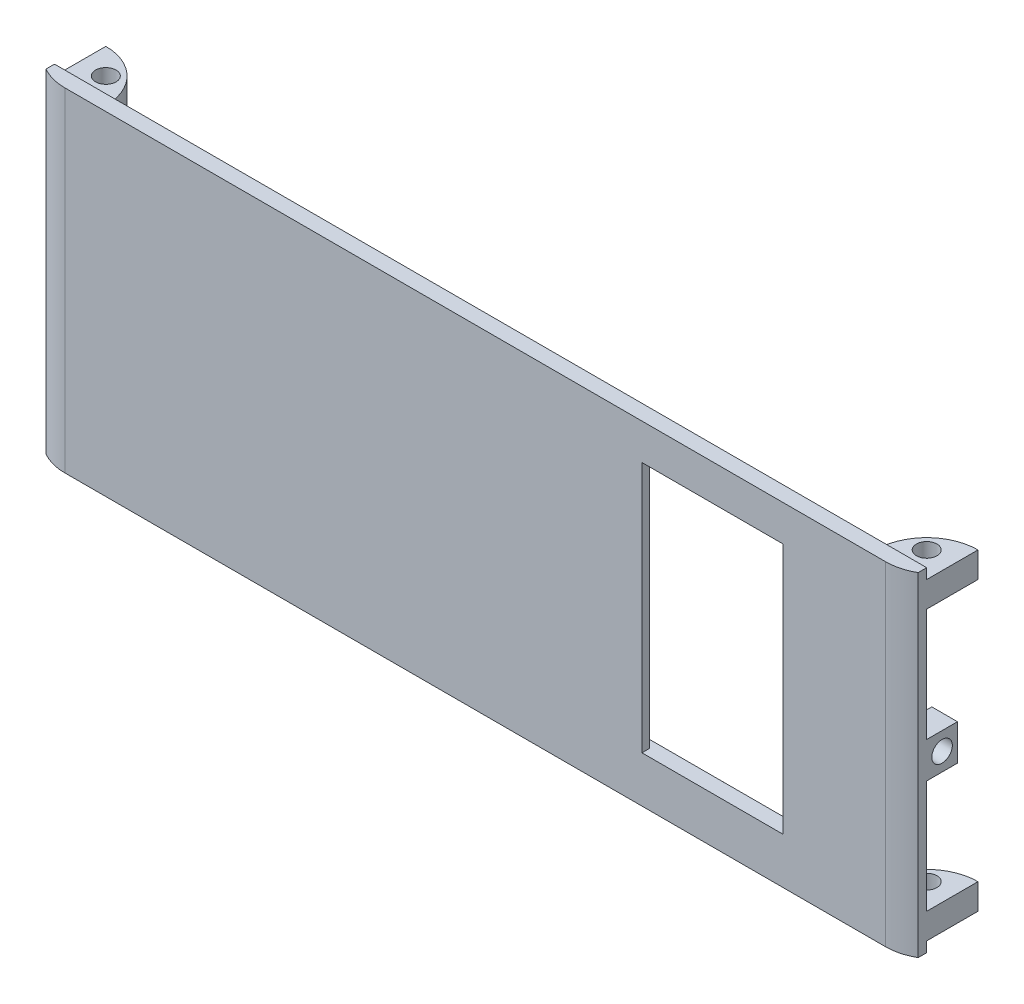
SolidWorks part; units mm, degrees
material "Allzweck-PBT"
ref_plane "Ebene vorne" through (0, 0, 0) normal (0, 0, 1) x (1, 0, 0)
ref_plane "Ebene oben" through (0, 0, 0) normal (0, 1, 0) x (1, 0, 0)
ref_plane "Ebene rechts" through (0, 0, 0) normal (1, 0, 0) x (0, 0, -1)
sketch "Skizze1" plane through (0, 0, 0) normal (0, 0, 1) x (1, 0, 0)
  line L1 (-90, 32.5) -> (90, 32.5)
  line L2 (-90, 32.5) -> (-90, -32.5)
  line L3 (-90, -32.5) -> (90, -32.5)
  line L4 (90, 32.5) -> (90, -32.5)
  line L5 (-90, 32.5) -> (90, -32.5) construction
  line L6 (-90, -32.5) -> (90, 32.5) construction
  point P0 (0, 0)
  dimension "D1" = 180
  dimension "3" = 65
extrude "Aufsatz-Linear austragen1" add sketch "Skizze1" along normal blind 3
sketch "Skizze3" plane through (0, 0, 0) normal (0, 0, -1) x (-1, 0, 0)
  line L0 (-90, -32.5) -> (-90, 32.5) construction
  line L9 (-85, 3.5) -> (-80, 3.5)
  line L10 (-85, 3.5) -> (-85, -3.5)
  line L11 (-85, -3.5) -> (-80, -3.5)
  line L12 (-80, 3.5) -> (-80, -3.5)
  line L13 (-85, 3.5) -> (-80, -3.5) construction
  line L14 (-85, -3.5) -> (-80, 3.5) construction
  line L15 (80, 3.5) -> (85, 3.5)
  line L16 (80, 3.5) -> (80, -3.5)
  line L17 (80, -3.5) -> (85, -3.5)
  line L18 (85, 3.5) -> (85, -3.5)
  line L19 (80, 3.5) -> (85, -3.5) construction
  line L20 (80, -3.5) -> (85, 3.5) construction
  line L21 (90, 32.5) -> (90, -32.5) construction
  line L23 (-90, 32.5) -> (90, 32.5) construction
  point P0 (-82.5, 0)
  point P5 (82.5, 0)
  dimension "D1" = 5
  dimension "D2" = 5
  dimension "7" = 7
  dimension "D3" = 5
  dimension "D4" = 7
  dimension "D5" = 5
  dimension "D6" = 32.5
  dimension "D7" = 32.5
extrude "Aufsatz-Linear austragen2" add sketch "Skizze3" along normal blind 6
hole_wizard "Ø4.0 (4) Durchmesser Bohrung1" positions "Skizze4" profile "Skizze5" hole size "Ø4.0" standard "DIN" end condition through all
sketch "Skizze4" plane through (-85, 0, 0) normal (-1, 0, 0) x (0, 0, 1)
  line L0 (0, -3.5) -> (0, 3.5) construction
  line L1 (-6, 3.5) -> (0, 3.5) construction
  point P0 (-3, 0)
  dimension "D1" = 3
  dimension "D2" = 3.5
sketch "Skizze5" plane through (-85, 0, -3) normal (0, 1, 0) x (0, 0, 1)
  line L0 (0, 0) -> (0, 175)
  line L1 (0, 175) -> (2, 175)
  line L2 (2, 175) -> (2, 0)
  line L5 (2, 0) -> (0, 0)
  line L11 (0, -6.35) -> (0, 107.95) construction
  dimension "Bohrerdurchmesser" = 4
  dimension "Bohrungstiefe" = 175
sketch "Skizze6" plane through (0, 32.5, 0) normal (0, 1, 0) x (1, 0, 0)
  line L0 (-80, -3) -> (-90, -3)
  line L9 (-90, -3) -> (-90, 0)
  line L10 (-90, 0) -> (-85, 0)
  line L11 (-85, 0) -> (-85, -1.6603)
  line L12 (80, -3) -> (90, -3)
  line L13 (90, -3) -> (90, 0)
  line L14 (90, 0) -> (85, 0)
  line L15 (85, 0) -> (85, -1.6603)
  arc A0 (80, -3) -> (85, -1.6603) centre (80, 7) ccw
  arc A1 (-80, -3) -> (-85, -1.6603) centre (-80, 7) cw
  point P12 (90, -3)
  point P15 (-90, -3)
  dimension "D1" = 10
  dimension "D3" = 10
  dimension "D2" = 1.3397
  dimension "D4" = 1.3397
  dimension "D5" = 10
extrude "Schnitt-Linear austragen1" cut sketch "Skizze6" against normal through all
sketch "Skizze7" plane through (0, 0, 3) normal (0, 0, 1) x (1, 0, 0)
  line L0 (80, -32.5) -> (80, 32.5) construction
  line L1 (32.5, 25.5) -> (60, 25.5)
  line L2 (32.5, 25.5) -> (32.5, -23.5)
  line L3 (32.5, -23.5) -> (60, -23.5)
  line L4 (60, 25.5) -> (60, -23.5)
  line L5 (-80, -32.5) -> (80, -32.5) construction
  dimension "D1" = 49
  dimension "D2" = 27.5
  dimension "D3" = 20
  dimension "D4" = 9
extrude "Schnitt-Linear austragen2" cut sketch "Skizze7" against normal through all
sketch "Skizze8" plane through (0, 0, 0) normal (0, 0, -1) x (-1, 0, 0)
  line L0 (-85, 32.5) -> (85, 32.5) construction
  line L1 (-85, 30.5) -> (-75, 30.5)
  line L2 (-85, 30.5) -> (-85, 25.5)
  line L3 (-85, 25.5) -> (-75, 25.5)
  line L4 (-75, 30.5) -> (-75, 25.5)
  line L5 (-85, 3.5) -> (-85, 32.5) construction
  dimension "D1" = 2
  dimension "D2" = 10
  dimension "D3" = 5
extrude "Aufsatz-Linear austragen3" add sketch "Skizze8" along normal blind 10
mirror "Spiegeln1" about plane through (0, 0, 0) normal (1, 0, 0) of "Aufsatz-Linear austragen3" second plane through (0, 0, 0) second plane normal (0, 1, 0)
fillet "Verrundung1" radius 10 20 edges at (75, 25.5, -5) (75, 30.5, -5) (80, 25.5, -10) (75, 28, -10) (80, 30.5, -10) (80, -30.5, -10) (75, -28, -10) (75, -30.5, -5) (80, -25.5, -10) (75, -25.5, -5) (-80, 30.5, -10) (-75, 28, -10) (-75, 30.5, -5) (-80, 25.5, -10) (-75, 25.5, -5) (-75, -25.5, -5) (-75, -30.5, -5) (-80, -25.5, -10) (-75, -28, -10) (-80, -30.5, -10)
hole_wizard "Ø4.0 (4) Durchmesser Bohrung2" positions "Skizze9" profile "Skizze10" hole size "Ø4.0" standard "DIN"
sketch "Skizze9" plane through (0, 30.5, 0) normal (0, 1, 0) x (1, 0, 0)
  line L0 (-85, 10) -> (-85, 0) construction
  line L1 (-75, 0) -> (-85, 0) construction
  line L2 (85, 0) -> (-85, 0) construction
  line L3 (85, 10) -> (85, 0) construction
  point P0 (-80, 5)
  point P2 (80, 5)
  dimension "D1" = 5
  dimension "D2" = 5
  dimension "D3" = 5
  dimension "D4" = 5
sketch "Skizze10" plane through (-80, 30.5, -5) normal (1, 0, 0) x (0, 0, 1)
  line L0 (0, 0) -> (0, 5)
  line L1 (0, 5) -> (2, 5)
  line L2 (2, 5) -> (2, 0)
  line L5 (2, 0) -> (0, 0)
  line L11 (0, -6.35) -> (0, 107.95) construction
  dimension "Bohrerdurchmesser" = 4
  dimension "Bohrungstiefe" = 5
hole_wizard "Ø4.0 (4) Durchmesser Bohrung3" positions "Skizze11" profile "Skizze12" hole size "Ø4.0" standard "DIN"
sketch "Skizze11" plane through (0, -30.5, 0) normal (0, -1, 0) x (-1, 0, 0)
  line L0 (-85, 10) -> (-85, 0) construction
  line L1 (-75, 0) -> (-85, 0) construction
  line L2 (85, 10) -> (85, 0) construction
  line L3 (75, 0) -> (85, 0) construction
  point P0 (-80, 5)
  point P2 (80, 5)
  dimension "D1" = 5
  dimension "D2" = 5
  dimension "D3" = 5
  dimension "D4" = 5
sketch "Skizze12" plane through (80, -30.5, -5) normal (1, 0, 0) x (0, 0, -1)
  line L0 (0, 0) -> (0, 5)
  line L1 (0, 5) -> (2, 5)
  line L2 (2, 5) -> (2, 0)
  line L5 (2, 0) -> (0, 0)
  line L11 (0, -6.35) -> (0, 107.95) construction
  dimension "Bohrerdurchmesser" = 4
  dimension "Bohrungstiefe" = 5
sketch "Skizze13" plane through (0, 0, 0) normal (0, 0, -1) x (-1, 0, 0)
  line L0 (-60, -23.5) -> (-60, 25.5) construction
  line L1 (-61.5, 25.5) -> (-31, 25.5)
  line L2 (-61.5, 25.5) -> (-61.5, -23.5)
  line L3 (-61.5, -23.5) -> (-31, -23.5)
  line L4 (-31, 25.5) -> (-31, -23.5)
  line L5 (-32.5, 25.5) -> (-32.5, -23.5) construction
  line L6 (-60, 25.5) -> (-32.5, 25.5) construction
  line L7 (-32.5, -23.5) -> (-60, -23.5) construction
  dimension "D1" = 1.5
  dimension "D2" = 1.5
extrude "Schnitt-Linear austragen4" cut sketch "Skizze13" against normal blind 1.5 contours L2 L1 L4 L3
